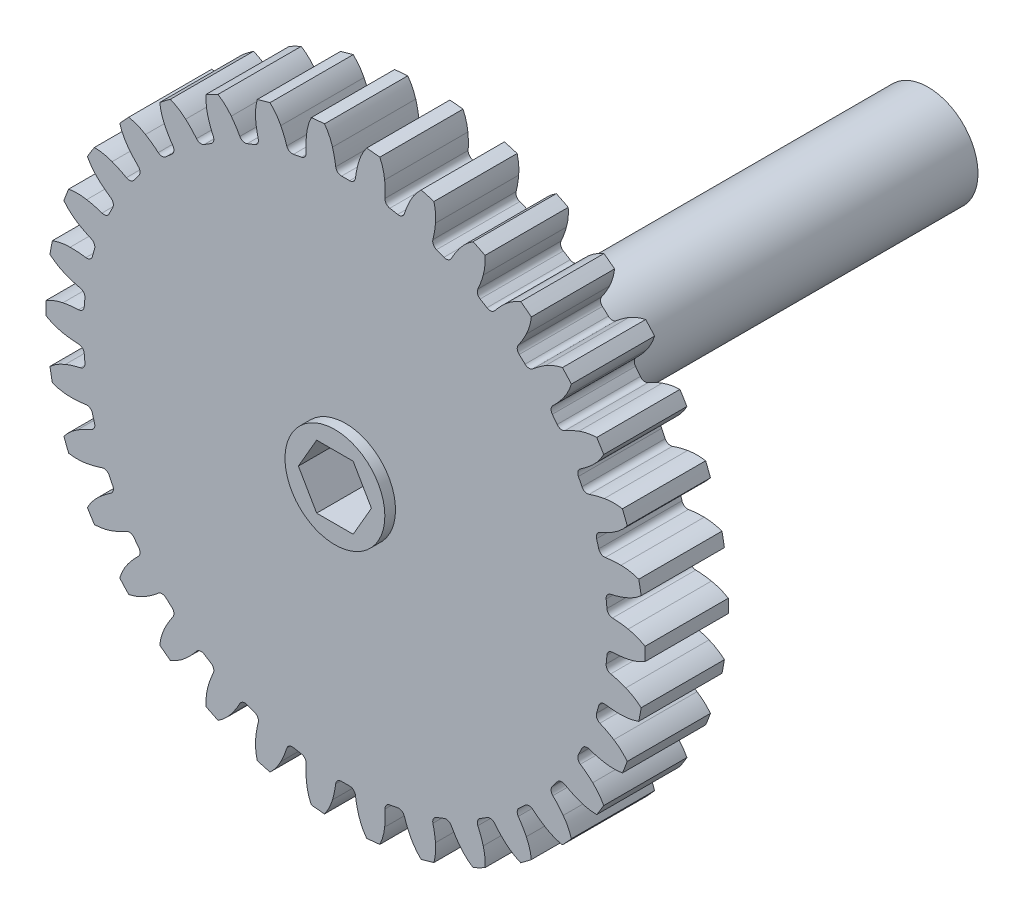
SolidWorks part; units mm, degrees
material "PLA/ABS"
ref_plane "Front" through (0, 0, 0) normal (0, 0, 1) x (1, 0, 0)
ref_plane "Top" through (0, 0, 0) normal (0, 1, 0) x (1, 0, 0)
ref_plane "Right" through (0, 0, 0) normal (1, 0, 0) x (0, 0, -1)
sketch "Sketch1" plane through (0, 0, 0) normal (0, 0, 1) x (1, 0, 0)
  line L0 (0, 0) -> (21.59, 0) construction
  line L1 (21.59, 0) -> (22.86, 0) construction
  circle A0 centre (0, 0) radius 21.59 construction
  circle A1 centre (0, 0) radius 22.86
  dimension "D1" = 43.18
  dimension "D2" = 1.27
extrude "Round Stock" add sketch "Sketch1" along normal mid plane 6.35
sketch "Sketch2" plane through (0, 0, 3.175) normal (0, 0, 1) x (1, 0, 0)
  line L0 (0, 0) -> (20.0025, 0) construction
  line L1 (20.0025, 0) -> (21.59, 0) construction
  line L2 (0, 0) -> (-22.86, 0) construction
  line L3 (0, 0) -> (-22.4708, -4.2005) construction
  line L4 (-22.5584, -3.7009) -> (-21.383, -2.9823) construction
  line L5 (-21.383, -2.9823) -> (-19.8439, -2.5135) construction
  line L6 (-22.8544, -0.5072) -> (-21.5669, -0.9976) construction
  line L7 (-21.5669, -0.9976) -> (-19.9679, -1.1756) construction
  line L8 (-21.1997, -3.9629) -> (-21.383, -2.9823) construction
  line L9 (-21.5669, -0.9976) -> (-21.5669, 0) construction
  line L12 (0, 0) -> (-21.5669, -0.9976) construction
  line L13 (0, 0) -> (-21.383, -2.9823) construction
  line L14 (-21.383, -2.9823) -> (-20.3452, -10.4237) construction
  line L15 (-21.5669, -0.9976) -> (-21.9141, 6.5078) construction
  line L16 (-21.383, -2.9823) -> (-21.5669, -0.9976) construction
  line L17 (-19.9172, -1.8456) -> (-19.9679, -1.1756) construction
  line L18 (-19.9172, -1.8456) -> (-19.8439, -2.5135) construction
  circle A0 centre (0, 0) radius 21.59 construction
  circle A1 centre (0, 0) radius 20.0025 construction
  circle A2 centre (0, 0) radius 22.86 construction
  arc A3 (-22.5584, -3.7009) -> (-22.8544, -0.5072) centre (0, 0) cw
  arc A4 (-19.8439, -2.5135) -> (-19.9679, -1.1756) centre (0, 0) cw construction
  arc A6 (-22.5584, -3.7009) -> (-21.383, -2.9823) centre (-19.9206, -6.695) cw
  arc A7 (-22.8544, -0.5072) -> (-21.5669, -0.9976) centre (-20.8116, 2.9206) ccw
  arc A8 (-21.383, -2.9823) -> (-20.2324, -2.6305) centre (-18.5705, -10.1225) cw
  arc A9 (-21.5669, -0.9976) -> (-20.3713, -1.132) centre (-20.1143, 6.5378) ccw
  arc A10 (-20.2324, -2.6305) -> (-19.8867, -2.1488) centre (-20.3287, -2.1965) ccw
  arc A11 (-20.3713, -1.132) -> (-19.943, -1.542) centre (-20.3862, -1.5763) cw
  arc A12 (-19.8867, -2.1488) -> (-19.943, -1.542) centre (0, 0) cw
  dimension "D6" = 43.18
  dimension "D9" = 0.4445
  dimension "D12" = 3.9903
  dimension "D2" = 1.5875
  dimension "D3" = 10.588
  dimension "D4" = 0.9976
  dimension "D5" = 0.9976
  dimension "D11" = 1.9932
  dimension "D8" = 14.5
  dimension "D7" = 14.5
  dimension "D14" = 9
  dimension "D15" = 9
extrude "Single Tooth" cut sketch "Sketch2" against normal through all
ref_axis "Axis" through (0, 0, 50) along (0, 0, -1)
pattern_circular "Tooth Pattern" count 34 over 360 about axis through (0, 0, 50) along (0, 0, -1) of "Single Tooth"
sketch "Sketch4" plane through (0, 0, 3.175) normal (0, 0, 1) x (1, 0, 0)
  circle A0 centre (0, 0) radius 3.1039
  dimension "D1" = 6.2078
extrude "TopBearingBoss" [suppressed] add sketch "Sketch4" along normal blind 0.635
mirror "BottomBearingBoss" [suppressed] about plane through (0, 0, 0) normal (0, 0, 1)
sketch "Sketch6" [suppressed] plane through (0, 0, 0) normal (0, 0, 1) x (1, 0, 0)
  line L1 (1.4005, 2.4257) -> (-1.4005, 2.4257)
  line L2 (-1.4005, 2.4257) -> (-2.801, 0)
  line L3 (-2.801, 0) -> (-1.4005, -2.4257)
  line L4 (-1.4005, -2.4257) -> (1.4005, -2.4257)
  line L5 (1.4005, -2.4257) -> (2.801, 0)
  line L6 (2.801, 0) -> (1.4005, 2.4257)
  circle A0 centre (0, 0) radius 2.4257 construction
  circle A1 centre (0, 0) radius 2.4257 construction
extrude "Hex" [suppressed] cut sketch "Sketch6" against normal through all both and the other way through all
sketch "Sketch7" plane through (0, 0, -3.175) normal (0, 0, -1) x (-1, 0, 0)
  line L7 (1.3931, -2.413) -> (2.7863, 0)
  line L8 (2.7863, 0) -> (1.3931, 2.413)
  line L9 (1.3931, 2.413) -> (-1.3931, 2.413)
  line L10 (-1.3931, 2.413) -> (-2.7863, 0)
  line L11 (-2.7863, 0) -> (-1.3931, -2.413)
  line L12 (-1.3931, -2.413) -> (1.3931, -2.413)
  circle A1 centre (0, 0) radius 2.413 construction
  dimension "D1" = 4.826
extrude "Cut-Extrude1" cut sketch "Sketch7" against normal through all
sketch "Sketch8" plane through (0, 0, -3.175) normal (0, 0, -1) x (-1, 0, 0)
  line L6 (1.3931, -2.413) -> (2.7863, 0)
  line L7 (-1.3931, -2.413) -> (1.3931, -2.413)
  line L8 (-2.7863, 0) -> (-1.3931, -2.413)
  line L9 (-1.3931, 2.413) -> (-2.7863, 0)
  line L10 (1.3931, 2.413) -> (-1.3931, 2.413)
  line L11 (2.7863, 0) -> (1.3931, 2.413)
  line L12 (1.3931, -2.413) -> (2.7863, 0)
  line L13 (-1.3931, -2.413) -> (1.3931, -2.413)
  line L14 (-2.7863, 0) -> (-1.3931, -2.413)
  line L15 (-1.3931, 2.413) -> (-2.7863, 0)
  line L16 (1.3931, 2.413) -> (-1.3931, 2.413)
  line L17 (2.7863, 0) -> (1.3931, 2.413)
  circle A2 centre (0, 0) radius 3.81
  dimension "D1" = 7.62
  dimension "D2" = 0
extrude "Boss-Extrude1" add sketch "Sketch8" along normal blind 38.1
chamfer "Chamfer1" distance 1.27 angle 45 1 edges at (3.81, 0, -3.175)
sketch "Sketch9" plane through (0, 0, 3.175) normal (0, 0, 1) x (1, 0, 0)
  line L6 (-1.3931, -2.413) -> (1.3931, -2.413)
  line L7 (-2.7863, 0) -> (-1.3931, -2.413)
  line L8 (-1.3931, 2.413) -> (-2.7863, 0)
  line L9 (1.3931, 2.413) -> (-1.3931, 2.413)
  line L10 (2.7863, 0) -> (1.3931, 2.413)
  line L11 (1.3931, -2.413) -> (2.7863, 0)
  line L12 (-1.3931, -2.413) -> (1.3931, -2.413)
  line L13 (-2.7863, 0) -> (-1.3931, -2.413)
  line L14 (-1.3931, 2.413) -> (-2.7863, 0)
  line L15 (1.3931, 2.413) -> (-1.3931, 2.413)
  line L16 (2.7863, 0) -> (1.3931, 2.413)
  line L17 (1.3931, -2.413) -> (2.7863, 0)
  circle A0 centre (0, 0) radius 3.81
  dimension "D2" = 7.62
  dimension "D1" = 0
extrude "Boss-Extrude2" add sketch "Sketch9" along normal blind 0.8128
equation "\"N_teeth\"= \"No_Teeth\""
equation "\"pitch_diameter\"= \"N_teeth\" / \"Pitch\""
equation "\"Pd\"=\"N_teeth\"/\"pitch_diameter\""
equation "\"addendum\"=1.000/\"Pd\""
equation "\"face_width\"=0.25"
equation "\"deddendum\"=1.250/\"Pd\""
equation "\"D3@Sketch2\" = 360/\"N_teeth\""
equation "\"tooth_thickness\"=1.571/\"Pd\""
equation "\"D4@Sketch2\" = \"tooth_thickness\"/2"
equation "\"D5@Sketch2\" = \"tooth_thickness\"/2"
equation "\"Pressure_Angle\"= iif ( \"Pitch\" = 20 , 14.500000 , iif ( \"Pitch\" = 32 , 20 , 20 ) )"
equation "\"base_fillet\"=0.35/\"Pd\""
equation "\"D12@Sketch2\" = 2*\"tooth_thickness\""
equation "\"hub_projection\"=0.250000"
equation "\"sss_diam\"= 0.062500"
equation "\"D1@Sketch1\"=\"pitch_diameter\""
equation "\"D2@Sketch1\"=\"addendum\""
equation "\"D1@Round Stock\" = \"face_width\""
equation "\"D2@Sketch2\"=\"deddendum\""
equation "\"D6@Sketch2\"=\"pitch_diameter\""
equation "\"D7@Sketch2\"=\"Pressure_Angle\""
equation "\"D8@Sketch2\"=\"D7@Sketch2\""
equation "\"D9@Sketch2\"=\"base_fillet\""
equation "\"D1@Tooth Pattern\" = \"N_teeth\""
equation "\"Pitch\"= \"GearPitch\""
equation "\"BossDia\"= \"BoreDia\" * 1.3"
equation "\"Hex\"= iif ( \"HexBore\" = 1 , \"unsuppressed\" , \"suppressed\" )"
equation "\"TopBearingBoss\" = iif ( \"Bearing_Boss\" = 0 , \"suppressed\" , \"unsuppressed\" )"
equation "\"BottomBearingBoss\"= iif ( \"Bearing_Boss\" > 1 , \"unsuppressed\" , \"suppressed\" )"
equation "\"D1@Sketch4\"=\"BossDia\""
equation "\"ToothCount\"= iif ( \"No_Teeth\" < 22 , \"suppressed\" , \"unsuppressed\" )"
